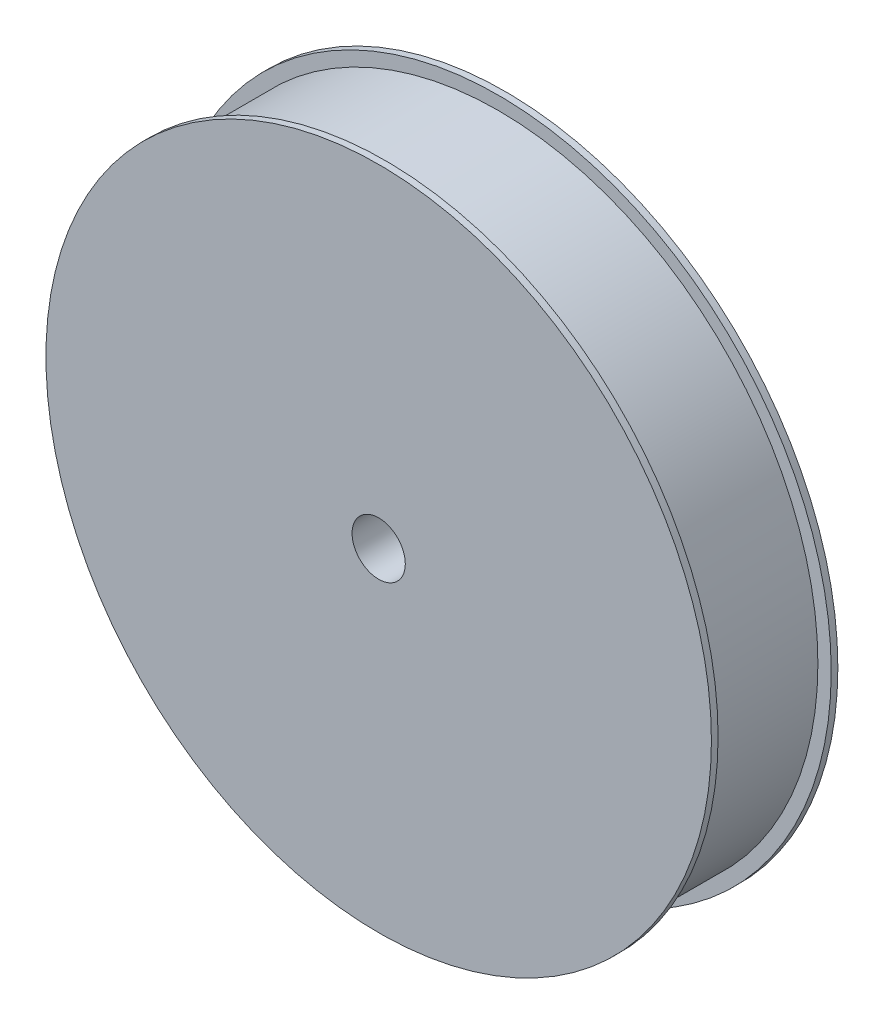
SolidWorks part; units mm, degrees
ref_plane "Front Plane" through (0, 0, 0) normal (0, 0, 1) x (1, 0, 0)
ref_plane "Top Plane" through (0, 0, 0) normal (0, 1, 0) x (1, 0, 0)
ref_plane "Right Plane" through (0, 0, 0) normal (1, 0, 0) x (0, 0, -1)
sketch "Inner" plane through (0, 0, 0) normal (0, 0, 1) x (1, 0, 0)
  circle A0 centre (0, 0) radius 76.2
  dimension "D1" = 152.4
extrude "Boss-Extrude1" add sketch "Inner" along normal blind 13.4937 contours A0
sketch "Rim" plane through (0, 0, 13.4937) normal (0, 0, 1) x (1, 0, 0)
  circle A0 centre (0, 0) radius 79.375
  circle A1 centre (0, 0) radius 76.2 construction
  dimension "D1" = 3.175
extrude "Boss-Extrude2" add sketch "Rim" along normal blind 1.5875
mirror "Mirror1" about plane through (0, 0, 0) normal (0, 0, 1) of bodies 102
sketch "Hole" plane through (0, 0, 15.0812) normal (0, 0, 1) x (1, 0, 0)
  circle A0 centre (0, 0) radius 6.35
  dimension "D1" = 12.7
extrude "Cut-Extrude1" cut sketch "Hole" against normal through all
